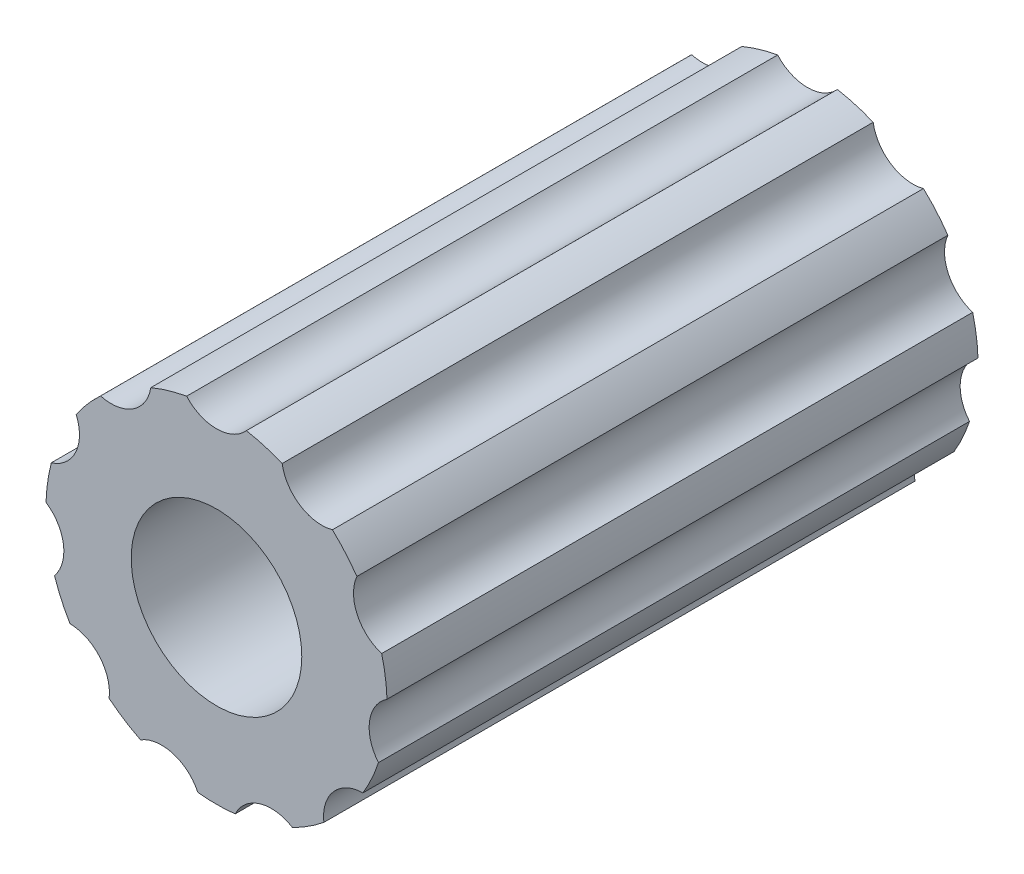
SolidWorks part; units mm, degrees
ref_plane "Front Plane" through (0, 0, 0) normal (0, 0, 1) x (1, 0, 0)
ref_plane "Top Plane" through (0, 0, 0) normal (0, 1, 0) x (1, 0, 0)
ref_plane "Right Plane" through (0, 0, 0) normal (1, 0, 0) x (0, 0, -1)
sketch "Sketch1" plane through (0, 0, 0) normal (0, 0, 1) x (1, 0, 0)
  circle A0 centre (0, 0) radius 6.35
  dimension "D1" = 12.7
extrude "Boss-Extrude1" add sketch "Sketch1" along normal blind 22
ref_axis "Axis1" through (0, 0, -1.1) along (0, 0, 1)
sketch "Sketch2" plane through (0, 0, 22) normal (0, 0, 1) x (1, 0, 0)
  line L0 (0, 0) -> (0, 7.2483) construction
  arc A0 (-1.1117, 6.2519) -> (1.1117, 6.2519) centre (0, 7.2483) ccw
  circle A1 centre (0, 0) radius 6.35 construction
  arc A2 (1.1117, 6.2519) -> (-1.1117, 6.2519) centre (0, 0) ccw
extrude "Cut-Extrude1" cut sketch "Sketch2" against normal through all
pattern_circular "CirPattern1" count 11 over 360 about axis through (0, 0, -1.1) along (0, 0, 1) of "Cut-Extrude1"
sketch "Sketch3" plane through (0, 0, 22) normal (0, 0, 1) x (1, 0, 0)
  circle A0 centre (0, 0) radius 3.175
  dimension "D1" = 6.35
extrude "Cut-Extrude2" cut sketch "Sketch3" against normal offset from surface (19 mm away) 3 up to face at (0, 0, 0)
sketch "Sketch4" plane through (0, 0, 3) normal (0, 0, 1) x (1, 0, 0)
  circle A0 centre (0, 0) radius 0.9525
  dimension "D1" = 1.905
extrude "Cut-Extrude3" cut sketch "Sketch4" against normal through all
